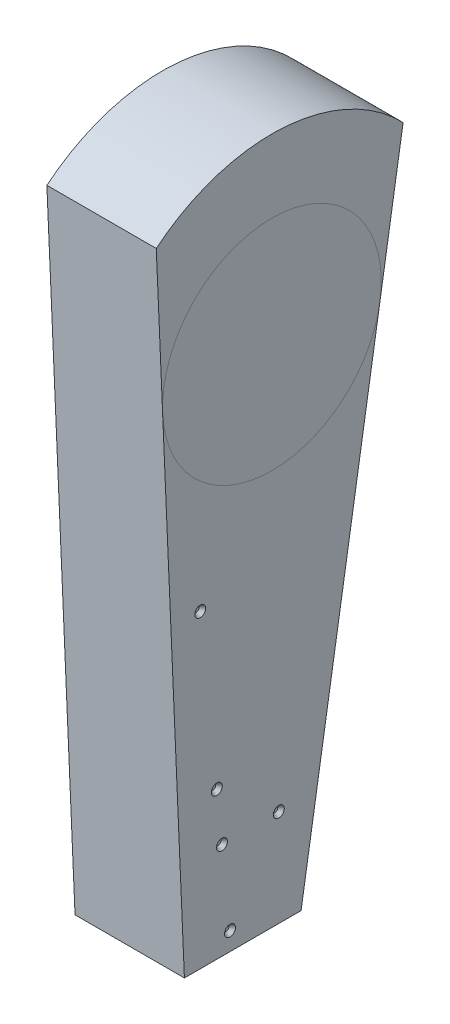
SolidWorks part; units mm, degrees
ref_plane "Alzado" through (0, 0, 0) normal (0, 0, 1) x (1, 0, 0)
ref_plane "Planta" through (0, 0, 0) normal (0, 1, 0) x (1, 0, 0)
ref_plane "Vista lateral" through (0, 0, 0) normal (1, 0, 0) x (0, 0, -1)
sketch "Croquis1" plane through (0, 0, 0) normal (1, 0, 0) x (0, 0, -1)
  line L0 (-60.94, -351.79) -> (-80.5516, 98.1857)
  line L1 (-20.3, -351.79) -> (-20.3, 125.3671) construction
  line L2 (20.34, -351.79) -> (91.4322, 88.1428)
  line L7 (-60.94, -351.79) -> (20.34, -351.79)
  circle A0 centre (0, 0) radius 127 construction
  circle A1 centre (0, 0) radius 76.2 construction
  arc A4 (91.4322, 88.1428) -> (-80.5516, 98.1857) centre (0, 0) ccw
  dimension "D1" = 254
  dimension "D2" = 152.4
  dimension "D4" = 81.28
  dimension "D3" = 20.3
  dimension "D5" = 351.79
extrude "Saliente-Extruir1" add sketch "Croquis1" along normal blind 76.2
sketch "Croquis2" plane through (76.2, 0, 0) normal (1, 0, 0) x (0, 0, -1)
  circle A0 centre (0, 0) radius 76.2
split line "Línea de partición1"
sketch "Croquis3" plane through (0, -351.79, 0) normal (0, -1, 0) x (1, 0, 0)
  line L1 (38.1, 20.3) -> (38.1, 60.94) construction
  line L2 (76.2, 60.94) -> (0, 60.94) construction
  circle A0 centre (38.1, 20.3) radius 25.4
  dimension "D1" = 50.8
  dimension "D2" = 40.64
split line "Línea de partición2"
sketch "Croquis4" plane through (76.2, 0, 0) normal (1, 0, 0) x (0, 0, -1)
  line L6 (-53.5213, -100.8643) -> (-29.1719, -339.09) construction
  line L7 (-29.1719, -339.09) -> (29.1719, -339.09) construction
  line L8 (29.1719, -339.09) -> (53.2304, -103.711) construction
  circle A0 centre (-49.9171, -136.1268) radius 3.81
  circle A1 centre (-38.3624, -249.174) radius 3.81
  circle A2 centre (-34.7681, -284.3391) radius 3.81
  circle A3 centre (-29.1719, -339.09) radius 3.81
  circle A4 centre (29.1719, -339.09) radius 3.81
  circle A5 centre (4.8195, -284.3391) radius 3.81
  dimension "D1" = 7.62
extrude "Cortar-Extruir1" cut sketch "Croquis4" against normal blind 2.54 draft 39
sketch "Croquis5" plane through (0, 0, 0) normal (-1, 0, 0) x (0, 0, 1)
  line L3 (0, -339.09) -> (0, -280.0103) construction
  line L6 (-29.1719, -339.09) -> (-72.8345, 88.0887) construction
  line L7 (72.8345, 88.0887) -> (29.1719, -339.09) construction
  line L8 (29.1719, -339.09) -> (-29.1719, -339.09) construction
  circle A1 centre (-12.5569, -339.09) radius 3.81
  arc A2 (72.8345, 88.0887) -> (-72.8345, 88.0887) centre (0, 0) ccw construction
  circle A3 centre (12.5569, -339.09) radius 3.81
  circle A4 centre (-34.1821, -290.0722) radius 3.81
  circle A5 centre (-48.2655, -152.2857) radius 3.81
  circle A6 centre (-69.7519, 57.9299) radius 3.81
  circle A7 centre (-48.2655, 103.6095) radius 3.81
  circle A8 centre (48.2655, 103.6095) radius 3.81
  circle A9 centre (69.7519, 57.9299) radius 3.81
  circle A10 centre (48.2655, -152.2857) radius 3.81
  dimension "D1" = 7.62
extrude "Cortar-Extruir2" cut sketch "Croquis5" against normal blind 2.54 draft 39
ref_point "点1"
ref_axis "Link3-line1" through (76.2, 0, 0) along (1, 0, 0)
ref_point "点2"
ref_point "点3"
ref_point "点4"
ref_plane "基准面1" through (38.1, 0, 0) normal (1, 0, 0) x (0, 0, -1)
ref_point "Link3-point1"
sketch "草图1" plane through (38.1, 0, 0) normal (1, 0, 0) x (0, 0, -1)
  line L0 (-20.3, -351.79) -> (-20.3, 125.3671) construction
  line L1 (-60.94, -351.79) -> (20.34, -351.79) construction
  arc A0 (91.4322, 88.1428) -> (-80.5516, 98.1857) centre (0, 0) ccw construction
ref_axis "Link3-line2" through (38.1, -351.79, 20.3) along (0, 1, 0)
ref_plane "基准面2" through (0, 0, 20.3) normal (0, 0, 1) x (0, 1, 0)
